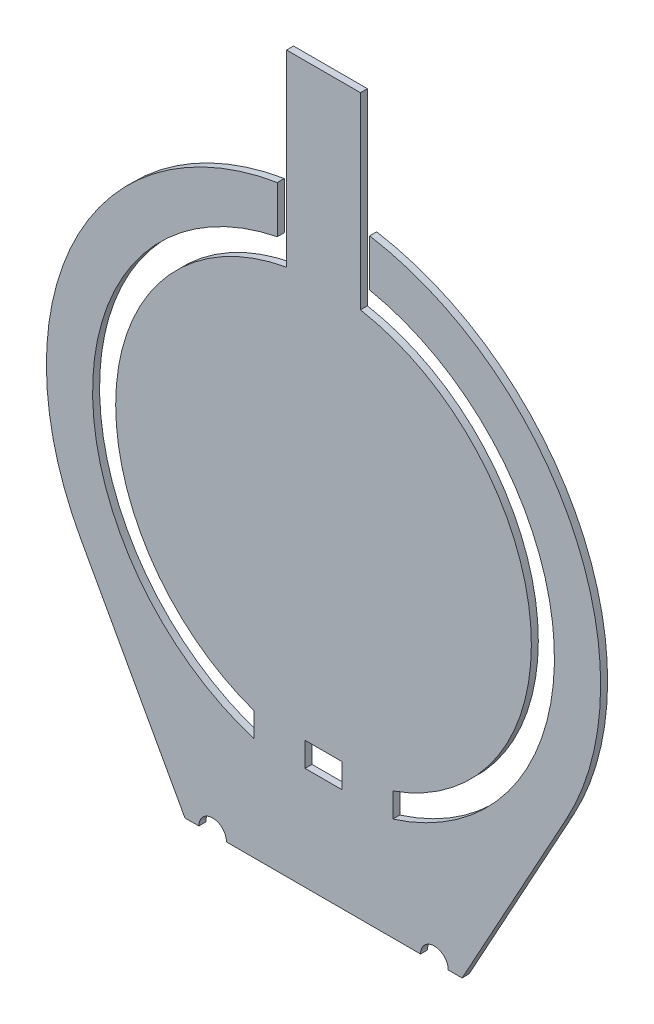
SolidWorks part; units mm, degrees
ref_plane "Plano frontal" through (0, 0, 0) normal (0, 0, 1) x (1, 0, 0)
ref_plane "Plano superior" through (0, 0, 0) normal (0, 1, 0) x (1, 0, 0)
ref_plane "Plano direito" through (0, 0, 0) normal (1, 0, 0) x (0, 0, -1)
sketch "Sketch1" plane through (0, 0, 0) normal (0, 0, 1) x (1, 0, 0)
  line L1 (-15, -35) -> (15, -35)
  line L4 (-15, -35) -> (-7.5, -35)
  line L7 (15, -35) -> (26.2929, -14.4459)
  line L9 (-7.5, -23.8485) -> (-7.5, -21.2132)
  line L12 (7.5, -23.8485) -> (7.5, -21.2132)
  line L16 (-15, -35) -> (-26.2929, -14.4459)
  line L17 (-15, -35) -> (-5, -35)
  arc A0 (7.5, -21.2132) -> (-7.5, -21.2132) centre (0, 0) ccw
  arc A1 (7.5, -23.8485) -> (-7.5, -23.8485) centre (0, 0) ccw
  arc A2 (26.2929, -14.4459) -> (-26.2929, -14.4459) centre (0, 0) ccw
  point P10 (0, -35)
  dimension "D1" = 45
  dimension "D2" = 50
  dimension "D3" = 60
  dimension "D5" = 30
  dimension "D8" = 2.6353
extrude "Boss-Extrude1" add sketch "Sketch1" along normal blind 0.7544 contours L7 A2 L16 A1 L12 A0 L9 L1 region at (0, -3.2473, 0)
sketch "Esboço1" plane through (0, 0, 0.7544) normal (0, 0, 1) x (1, 0, 0)
  line L0 (0, 30) -> (0, 25)
  line L1 (-5, 27.5) -> (5, 27.5)
  line L3 (-5, 24.0986) -> (5, 24.0986)
  line L4 (-5, 24.0986) -> (-5, 30.9014)
  line L5 (-5, 30.9014) -> (5, 30.9014)
  line L6 (5, 24.0986) -> (5, 30.9014)
  line L7 (-5, 24.0986) -> (5, 30.9014) construction
  line L8 (-5, 30.9014) -> (5, 24.0986) construction
  arc A2 (26.2929, -14.4459) -> (-26.2929, -14.4459) centre (0, 0) ccw construction
  arc A3 (7.5, -23.8485) -> (-7.5, -23.8485) centre (0, 0) ccw construction
  point P8 (0, 27.5)
  point P11 (0, 27.5)
  arc M6 (-7.5, -23.8485) -> (7.5, -23.8485) centre (0, 0) cw
  arc M11 (26.2929, -14.4459) -> (-26.2929, -14.4459) centre (0, 0) ccw
  dimension "D1" = 10
extrude "Corte-extrusão1" cut sketch "Esboço1" against normal blind 10 contours L6 L5 L4 M11 | L4 L1 L0 M11 | L1 L6 L0 M11 | L6 L1 L0 M6 | L4 L0 L1 M6 | L3 L6 L4 M6 region at (2.426, 28.6836, 0.7544) region at (0, 30.3735, 0.7544) region at (-2.426, 28.6836, 0.7544) region at (2.5787, 26.1619, 0.7544) region at (-2.5787, 26.1619, 0.7544) region at (0, 24.4809, 0.7544)
sketch "Esboço3" plane through (0, 0, 0.7544) normal (0, 0, 1) x (1, 0, 0)
  line L0 (0, 22.5) -> (0, 42.5)
  line L1 (0, 22.5) -> (0, 20.9256)
  line L3 (-5, 24.4949) -> (-4, 24.4949)
  line L4 (-4, 20.9256) -> (4, 20.9256)
  line L5 (-4, 20.9256) -> (-4, 42.5)
  line L6 (4, 20.9256) -> (4, 42.5)
  line L7 (4, 42.5) -> (-4, 42.5)
  arc A2 (7.5, -21.2132) -> (-7.5, -21.2132) centre (0, 0) ccw construction
  arc M14 (7.5, -21.2132) -> (-7.5, -21.2132) centre (0, 0) ccw
  dimension "D1" = 20
  dimension "D2" = 1
  dimension "D3" = 8
extrude "Ressalto-extrusão1" add sketch "Esboço3" against normal blind 0.7544 contours L0 L7 L5 M14 | L6 L7 L0 M14 region at (-2.0059, 32.4402, 0.7544) region at (2.0059, 32.4402, 0.7544)
sketch "Esboço4" plane through (0, 0, 0.7544) normal (0, 0, 1) x (1, 0, 0)
  line L0 (-15, -35) -> (-12, -35)
  line L1 (-15, -35) -> (15, -35) construction
  line L2 (0, -35) -> (0, -27.9219)
  circle A0 centre (-12, -35) radius 1.5
  circle A1 centre (12, -35) radius 1.5
  line M8 (-15, -35) -> (15, -35)
  dimension "D2" = 3
  dimension "D1" = 3
extrude "Corte-extrusão2" cut sketch "Esboço4" against normal blind 10 contours A0 L0 M8 | A1 M8 region at (-12, -34.3634, 0.7544) region at (12, -34.3634, 0.7544)
sketch "Esboço5" plane through (0, 0, 0.7544) normal (0, 0, 1) x (1, 0, 0)
  line L0 (-7.5, -23.8485) -> (7.5, -23.8485)
  line L1 (-7.5, -21.2132) -> (7.5, -21.2132)
  line L2 (-7.5, -22.5308) -> (7.5, -22.5308)
  line L3 (-7.5, -23.8485) -> (-7.5, -21.2132) construction
  line L4 (7.5, -23.8485) -> (7.5, -21.2132) construction
  line L6 (-2, -23.8485) -> (2, -23.8485)
  line L7 (-2, -23.8485) -> (-2, -21.2132)
  line L8 (-2, -21.2132) -> (2, -21.2132)
  line L9 (2, -23.8485) -> (2, -21.2132)
  line L10 (-2, -23.8485) -> (2, -21.2132) construction
  line L11 (-2, -21.2132) -> (2, -23.8485) construction
  point P14 (0, -22.5308)
  dimension "D1" = 4
extrude "Corte-extrusão3" cut sketch "Esboço5" against normal blind 10 contours L2 L9 L1 L7 | L0 L9 L2 L7 region at (0, -23.1897, 0.7544) region at (0, -21.872, 0.7544)
